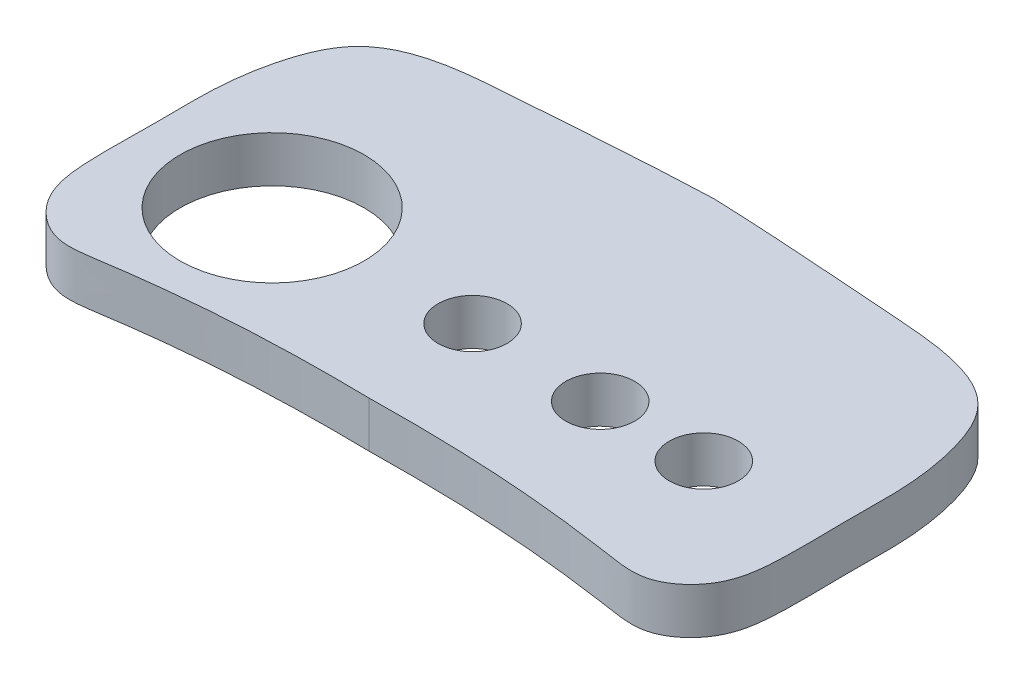
SolidWorks part; units mm, degrees
ref_plane "Ön Düzlem" through (0, 0, 0) normal (0, 0, 1) x (1, 0, 0)
ref_plane "Üst Düzlem" through (0, 0, 0) normal (0, 1, 0) x (1, 0, 0)
ref_plane "Sağ Düzlem" through (0, 0, 0) normal (1, 0, 0) x (0, 0, -1)
sketch "Çizim1" plane through (0, 0, 0) normal (0, 1, 0) x (1, 0, 0)
  line L0 (0, 17.9288) -> (0, -12.0712) construction
  line L1 (0, 0) -> (-30, 0) construction
  line L2 (-108.3091, -42.1463) -> (-63.9653, -42.1463) construction
  spline S0 degree 3 poles (0, 17.9288) (-5.8202, 17.7095) (-13.9034, 17.0426) (-26.8757, 16.196) (-29.5503, 8.9293) (-30.0905, 4.3361) (-29.9407, -0.8874) (-30.1549, -5.7017) (-29.6372, -10.9288) (-26.0312, -14.0818) (-15.7201, -12.3493) (-7.8072, -11.9389) (0, -12.0712) knots 0 0 0 0 0.19846 0.336013 0.394477 0.45973 0.505377 0.582751 0.635933 0.690009 0.731881 1 1 1 1
  spline S1 degree 3 poles (0, 17.9288) (5.8202, 17.7095) (13.9034, 17.0426) (26.8757, 16.196) (29.5503, 8.9293) (30.0905, 4.3361) (29.9407, -0.8874) (30.1549, -5.7017) (29.6372, -10.9288) (26.0312, -14.0818) (15.7201, -12.3493) (7.8072, -11.9389) (0, -12.0712) knots 0 0 0 0 0.19846 0.336013 0.394477 0.45973 0.505377 0.582751 0.635933 0.690009 0.731881 1 1 1 1
  dimension "D1" = 30
  dimension "D2" = 30
extrude "Yükseklik-Ekstrüzyon1" add sketch "Çizim1" along normal blind 4
sketch "Çizim2" plane through (0, 4, 0) normal (0, 1, 0) x (1, 0, 0)
  circle A0 centre (-18.5277, -1.9625) radius 8
  circle A1 centre (-1.1023, -1.9625) radius 3
  circle A2 centre (10.2935, -2.262) radius 3
  circle A3 centre (19.2935, -2.262) radius 3
  dimension "D1" = 16
  dimension "D2" = 6
  dimension "D3" = 9
extrude "Kes-Ekstrüzyon1" cut sketch "Çizim2" against normal blind 10
